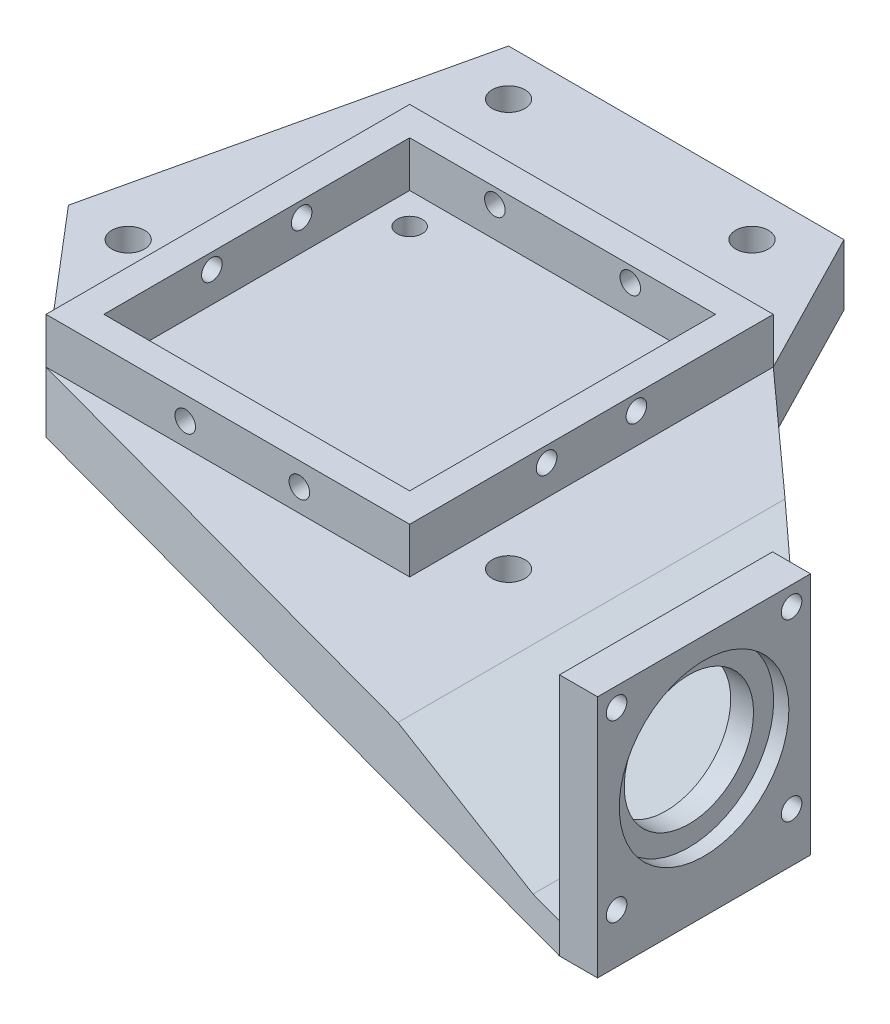
SolidWorks part; units mm, degrees
ref_plane "Front Plane" through (0, 0, 0) normal (0, 0, 1) x (1, 0, 0)
ref_plane "Top Plane" through (0, 0, 0) normal (0, 1, 0) x (1, 0, 0)
ref_plane "Right Plane" through (0, 0, 0) normal (1, 0, 0) x (0, 0, -1)
sketch "Sketch1" plane through (0, 0, 0) normal (0, 1, 0) x (1, 0, 0)
  line L0 (-20.1, 20.1) -> (20.1, -20.1) construction
  line L1 (-20.1, 20.1) -> (20.1, 20.1)
  line L2 (-20.1, 20.1) -> (-20.1, -20.1)
  line L3 (-20.1, -20.1) -> (20.1, -20.1)
  line L4 (20.1, 20.1) -> (20.1, -20.1)
  line L5 (-20.1, -20.1) -> (20.1, 20.1) construction
  line L6 (-23.9, 23.9) -> (-23.9, -23.9)
  line L7 (-23.9, -23.9) -> (23.9, -23.9)
  line L8 (23.9, 23.9) -> (23.9, -23.9)
  line L9 (-23.9, 23.9) -> (23.9, 23.9)
  point P4 (0, 0)
  dimension "D1" = 40.2
  dimension "D2" = 40.2
  dimension "D3" = 3.8
extrude "Boss-Extrude1" add sketch "Sketch1" along normal blind 6
sketch "Sketch6" plane through (0, 0, -23.9) normal (0, 0, -1) x (-1, 0, 0)
  line L0 (-8.9, 4) -> (8.9, 4) construction
  line L1 (23.9, 6) -> (23.9, 0) construction
  line L2 (-23.9, 6) -> (23.9, 6) construction
  circle A0 centre (-8.9, 4) radius 1.35
  circle A1 centre (8.9, 4) radius 1.35
  point P4 (0, 4)
  dimension "D3" = 2.7
  dimension "D4" = 2.7
  dimension "D1" = 15
  dimension "D2" = 2
extrude "Cut-Extrude4" cut sketch "Sketch6" against normal up to next
sketch "Sketch7" plane through (0, 0, 23.9) normal (0, 0, 1) x (1, 0, 0)
  line L0 (23.9, 6) -> (23.9, 0) construction
  line L1 (-23.9, 6) -> (-23.9, 0) construction
  line L2 (-23.9, 6) -> (-23.9, 0) construction
  circle A0 centre (9.4, 3) radius 1.35
  circle A1 centre (-5.6, 3) radius 1.35
  point P9 (-23.9, 3)
  dimension "D1" = 2.7
  dimension "D2" = 2.7
  dimension "D3" = 14.5
  dimension "D4" = 15
extrude "Cut-Extrude5" cut sketch "Sketch7" against normal up to next
sketch "Sketch8" plane through (23.9, 0, 0) normal (1, 0, 0) x (0, 0, -1)
  line L0 (-23.9, 6) -> (-23.9, 0) construction
  line L2 (0, 0) -> (0, 6) construction
  line L3 (-23.9, 6) -> (23.9, 6) construction
  circle A0 centre (-5.9, 4) radius 1.35
  circle A3 centre (5.9, 4) radius 1.35
  dimension "D3" = 2.7
  dimension "D1" = 18
  dimension "D2" = 2
extrude "Cut-Extrude6" cut sketch "Sketch8" against normal through all
sketch "Sketch10" plane through (23.9, 0, 0) normal (1, 0, 0) x (0, 0, -1)
  line L3 (-20.1, 0) -> (-49.9314, 0)
  line L6 (-23.9, 0) -> (23.9, 0) construction
  line L7 (-20.1, 0) -> (-20.1, 6)
  line L8 (-20.1, 6) -> (20.1, 6) construction
  line L9 (-20.1, 6) -> (20.1, 6) construction
  line L10 (-49.9314, 7.235) -> (-49.9314, 0)
  line L13 (-49.9314, 7.235) -> (-45.1764, 16.4549)
  line L14 (-45.1764, 16.4549) -> (-44.2876, 15.9965)
  line L15 (-25.4, 11.4128) -> (-24.4, 11.4128)
  line L16 (-20.1, 6) -> (-24.4, 6)
  line L17 (-24.4, 6) -> (-24.4, 11.4128)
  circle A0 centre (-35.4, 11.4128) radius 8.5 construction
  arc A2 (-44.2876, 15.9965) -> (-25.4, 11.4128) centre (-35.4, 11.4128) ccw
  arc A3 (-45.1764, 16.4549) -> (-24.4, 11.4128) centre (-35.4, 11.4128) ccw construction
  dimension "D2" = 17
  dimension "D1" = 20
  dimension "D3" = 22
  dimension "D5" = 5.4128
  dimension "D6" = 15.3
  dimension "D7" = 0.5
sketch "Sketch11" plane through (0, 0, 0) normal (0, 1, 0) x (1, 0, 0)
  line L0 (20.1, 20.1) -> (-20.1, 20.1) construction
  line L1 (-20.1, 20.1) -> (-20.1, -20.1) construction
  line L3 (23.9, -23.9) -> (23.9, 23.9) construction
  line L4 (73.9, -21.2) -> (68.9, -21.2)
  line L5 (73.9, -21.2) -> (73.9, -49.2)
  line L6 (73.9, -49.2) -> (68.9, -49.2)
  line L7 (68.9, -21.2) -> (68.9, -49.2)
  line L8 (68.9, -49.2) -> (-23.9, -23.9)
  line L9 (23.9, 23.9) -> (-23.9, 23.9)
  line L10 (23.9, 23.9) -> (23.9, -23.9)
  line L11 (23.9, -23.9) -> (-23.9, -23.9)
  line L12 (-23.9, 23.9) -> (-23.9, -23.9)
  line L13 (73.9, -21.2) -> (23.9, 23.9)
  circle A0 centre (-16, 16) radius 1.65
  circle A1 centre (16, 16) radius 1.65
  circle A2 centre (16, -16) radius 1.65
  circle A3 centre (-16, -16) radius 1.65
  point P24 (23.9, -35.4)
  point P27 (68.9, -35.2)
  dimension "D3" = 3.3
  dimension "D1" = 4.1
  dimension "D2" = 4.1
  dimension "D6" = 32
  dimension "D7" = 32
  dimension "D8" = 50
  dimension "D9" = 5
  dimension "D10" = 28
  dimension "D11" = 0.2
  dimension "D4" = 2
  dimension "D5" = 2
extrude "Boss-Extrude8" add sketch "Sketch11" against normal blind 8 contours L4 L13 L10 L11 L8 L7 | L4 L7 L6 L5 | L9 L12 L11 L10 A3 A2 A1 A0 region at (71.4, 0, 35.2) region at (39.5995, 0, 19.6661) region at (0, 0, 0)
sketch "Sketch12" plane through (73.9, 0, 0) normal (1, 0, 0) x (0, 0, -1)
  line L0 (-46.7, 21.5128) -> (-23.7, 21.5128) construction
  line L1 (-21.2, -3.9872) -> (-49.2, -3.9872)
  line L2 (-21.2, -3.9872) -> (-21.2, 24.0128)
  line L3 (-21.2, 24.0128) -> (-49.2, 24.0128)
  line L4 (-49.2, -3.9872) -> (-49.2, 24.0128)
  line L5 (-21.2, -3.9872) -> (-49.2, 24.0128) construction
  line L6 (-21.2, 24.0128) -> (-49.2, -3.9872) construction
  line L7 (-46.7, 21.5128) -> (-46.7, -1.4872) construction
  circle A0 centre (-35.2, 10.0128) radius 8.5
  circle A2 centre (-35.2, 10.0128) radius 11.15
  circle A3 centre (-46.7, 21.5128) radius 1.35
  circle A4 centre (-23.7, 21.5128) radius 1.35
  circle A5 centre (-23.7, -1.4872) radius 1.35
  circle A6 centre (-46.7, -1.4872) radius 1.35
  point P0 (-35.2, 10.0128)
  point P24 (-35.4, 11.4128)
  line M2 (-21.2, 0) -> (-49.2, 0)
  line M3 (-49.2, 0) -> (-49.2, -8)
  line M5 (-21.2, -8) -> (-21.2, 0)
  dimension "D1" = 22.3
  dimension "D4" = 2.7
  dimension "D10" = 17
  dimension "D2" = 28
  dimension "D3" = 28
  dimension "D7" = 23
  dimension "D8" = 23
  dimension "D9" = 11.5
  dimension "D11" = 0.2
  dimension "D12" = 1.4
  dimension "D5" = 2
  dimension "D6" = 2
sketch "Sketch13" plane through (0, 0, 49.2) normal (0, 0, 1) x (1, 0, 0)
  line L1 (73.9, -3.9872) -> (64.1144, -3.9872)
  line L2 (73.9, -3.9872) -> (73.9, 1.7874)
  line L3 (73.9, 1.7874) -> (28.7381, 1.7874)
  line L4 (64.1144, -3.9872) -> (28.7381, 1.7874)
  line L5 (73.9, -8) -> (73.9, 0) construction
extrude "Cut-Extrude7" cut sketch "Sketch13" against normal through all
extrude "Boss-Extrude9" add sketch "Sketch12" against normal blind 5 contours A6 A2 A5 L2 L3 L4 A4 A3 M2 | A6 L1 A5 A2 M2 M3 M5 region at (73.9, -2.1808, 35.2) region at (73.9, 0.3689, 25.7471)
extrude "Boss-Extrude10" add sketch "Sketch12<3>" against normal blind 3 from offset 2 contours A2 A0 M2 | A2 M2 region at (73.9, 0.3074, 35.2) region at (73.9, -0.4569, 35.2) offset against normal yes
sketch "Sketch12<3>" plane through (73.9, 0, 0) normal (1, 0, 0) x (0, 0, -1) same geometry as "Sketch12"
sketch "Sketch14" plane through (0, -8, 0) normal (0, -1, 0) x (1, 0, 0)
  line L0 (-33, -46) -> (17, 4) construction
  line L1 (-24, -37) -> (8, -37) construction
  line L2 (-24, -37) -> (-24, -5) construction
  line L3 (-24, -5) -> (8, -5) construction
  line L4 (8, -37) -> (8, -5) construction
  line L5 (-33, -46) -> (17, -46) construction
  line L6 (-33, -46) -> (-33, 4) construction
  line L7 (-33, 4) -> (17, 4) construction
  line L8 (17, -46) -> (17, 4) construction
  line L9 (-33, 4) -> (17, -46) construction
  line L10 (23.9, -23.9) -> (-23.9, -23.9) construction
  line L11 (-23.9, -23.9) -> (-23.9, 23.9) construction
  line L12 (23.9, -23.9) -> (-23.9, -23.9)
  line L13 (-23.9, -23.9) -> (-23.9, 23.9)
  line L14 (-23.9, 23.9) -> (-40.852, 4)
  line L15 (-40.852, 4) -> (-30.0457, -43.0457)
  line L16 (-30.0457, -43.0457) -> (14.0457, -43.0457)
  line L17 (14.0457, -43.0457) -> (23.9, -23.9)
  circle A0 centre (-24, -37) radius 2.15
  circle A1 centre (8, -37) radius 2.15
  circle A2 centre (8, -5) radius 2.15
  circle A3 centre (-24, -5) radius 2.15
  circle A4 centre (-33, 4) radius 2.15
  circle A7 centre (17, 4) radius 2.15
  circle A8 centre (29.5, 16.5) radius 2.15
  point P22 (-8, -21)
  point P23 (0, 0)
  line M27 (-23.9, 23.9) -> (-23.9, -23.9)
  line M28 (-23.9, -23.9) -> (23.9, -23.9)
  dimension "D5" = 4.3
  dimension "D6" = 4.3
  dimension "D7" = 4.3
  dimension "D8" = 4.3
  dimension "D11" = 4.3
  dimension "D12" = 4.3
  dimension "D10" = 4.3
  dimension "D1" = 50
  dimension "D2" = 32
  dimension "D3" = 32
  dimension "D4" = 50
  dimension "D13" = 8
  dimension "D14" = 21
  dimension "D9" = 37.5
extrude "Boss-Extrude11" add sketch "Sketch14" against normal up to surface (8 mm away) contours A3 L14 L15 L16 L17 A4 A1 A0 M27 M28 | L13 A3 region at (18.1447, -8, -33.0466) region at (-24.8587, -8, -5) up to face at (20.6552, 0, 11.0954)
extrude "Cut-Extrude8" cut sketch "Sketch14<3>" against normal blind 10 contours A8
sketch "Sketch14<3>" plane through (0, -8, 0) normal (0, -1, 0) x (1, 0, 0) same geometry as "Sketch14"
equation "\"D6@Sketch14\"=\"D5@Sketch14\""
equation "\"D7@Sketch14\"=\"D5@Sketch14\""
equation "\"D8@Sketch14\"=\"D5@Sketch14\""
equation "\"D11@Sketch14\"=\"D5@Sketch14\""
equation "\"D12@Sketch14\"=\"D8@Sketch14\""
equation "\"D10@Sketch14\"=\"D5@Sketch14\""
